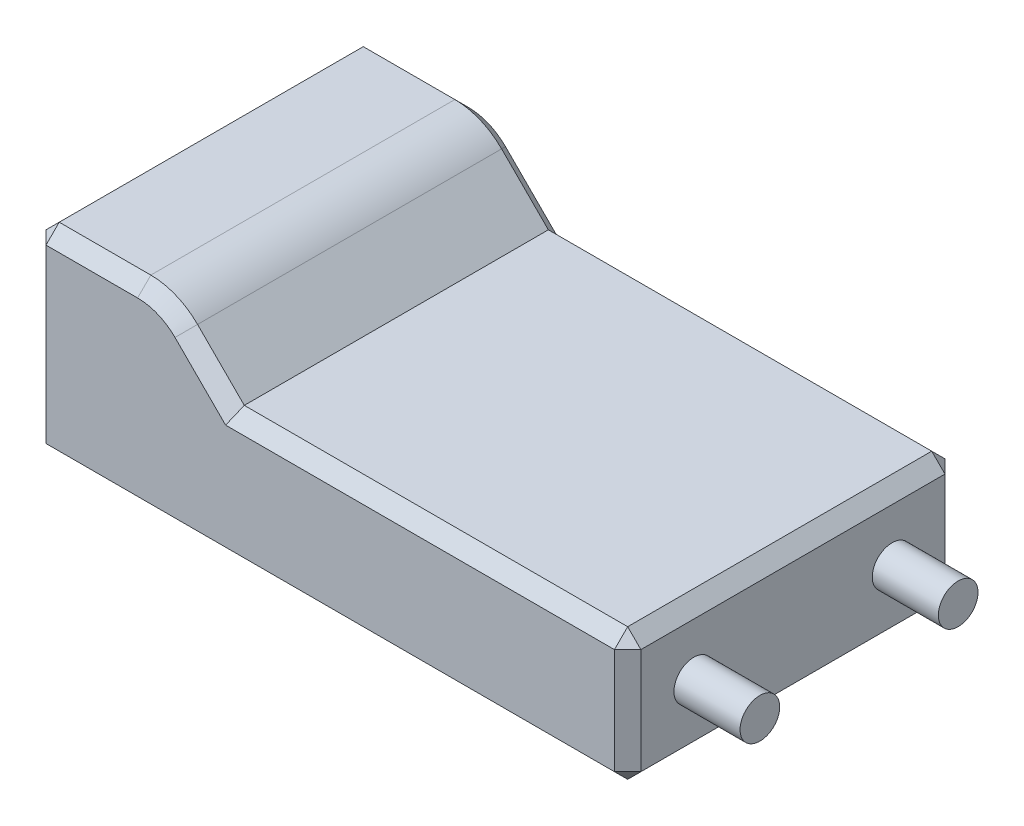
SolidWorks part; units mm, degrees
note: The reader was unsure of these and kept them because the rebuilt part matched: shared geometry of "草图1<4>".
ref_plane "前视基准面" through (0, 0, 0) normal (0, 0, 1) x (1, 0, 0)
ref_plane "上视基准面" through (0, 0, 0) normal (0, 1, 0) x (1, 0, 0)
ref_plane "右视基准面" through (0, 0, 0) normal (1, 0, 0) x (0, 0, -1)
sketch "草图1" plane through (0, 0, 0) normal (0, 1, 0) x (1, 0, 0)
  line L8 (-22.5, 12.5) -> (22.5, 12.5)
  line L9 (-22.5, 12.5) -> (-22.5, -12.5)
  line L10 (22.5, 12.5) -> (22.5, -12.5)
  line L11 (-22.5, -12.5) -> (22.5, -12.5)
  line L12 (-22.5, 12.5) -> (22.5, -12.5) construction
  line L13 (22.5, 12.5) -> (-22.5, -12.5) construction
  line L14 (-22.5, 12.5) -> (-12.5, 12.5)
  line L15 (-12.5, 12.5) -> (-12.5, -12.5)
  point P1 (0, 0)
  dimension "D1" = 45
  dimension "D2" = 25
  dimension "D3" = 10
extrude "凸台-拉伸1" add sketch "草图1" along normal blind 10 contours L8 L15 L11 L10
extrude "凸台-拉伸2" add sketch "草图1<4>" along normal blind 15 contours L15 L8 L9 L11
sketch "草图1<4>" plane through (0, 0, 0) normal (0, 1, 0) x (1, 0, 0) same geometry as "草图1"
sketch "草图2" plane through (-22.5, 0, 0) normal (-1, 0, 0) x (0, 0, 1)
  line L0 (0, 15) -> (0, 0)
  line L1 (-12.5, 15) -> (12.5, 15) construction
  line L2 (-10, 14) -> (10, 14)
  line L3 (-10, 14) -> (-10, 1)
  line L4 (10, 14) -> (10, 1)
  line L5 (-10, 1) -> (10, 1)
  line L6 (-10, 14) -> (10, 1) construction
  line L7 (10, 14) -> (-10, 1) construction
  point P6 (0, 7.5)
  dimension "D1" = 20
  dimension "D2" = 13
extrude "切除-拉伸1" cut sketch "草图2" against normal blind 7 contours L0 L5 L4 L2 | L3 L5 L0 L2
sketch "草图3" plane through (0, 0, 12.5) normal (0, 0, 1) x (1, 0, 0)
  line L0 (-12.5, 15) -> (-12.5, 10)
  line L1 (-12.5, 15) -> (-12.5, 10)
  line L2 (-12.5, 10) -> (-10, 10)
  line L3 (-12.5, 12.5) -> (-12.5, 10)
  line L4 (-12.5, 15) -> (-7.5, 10)
  dimension "D1" = 2.5
extrude "凸台-拉伸3" add sketch "草图3" against normal through all
fillet "圆角1" radius 5 1 edges at (-12.5, 15, 0)
chamfer "倒角1" distance 1 angle 45 18 edges at (-9.2678, 11.7678, -12.5) (-12.6577, 14.6194, -12.5) (7.5, 10, 12.5) (22.5, 5, 12.5) (0, 0, 12.5) (-22.5, 7.5, 12.5) (-9.2678, 11.7678, 12.5) (-12.6577, 14.6194, 12.5) (-18.5355, 15, 12.5) (-22.5, 0, 0) (22.5, 0, 0) (22.5, 10, 0) (7.5, 10, -12.5) (22.5, 5, -12.5) (0, 0, -12.5) (-22.5, 7.5, -12.5) (-18.5355, 15, -12.5) (-22.5, 15, 0)
sketch "草图5" plane through (22.5, 0, 0) normal (1, 0, 0) x (0, 0, -1)
  line L0 (-11.5, 5) -> (-7.5, 5)
  line L1 (-11.5, 9) -> (-11.5, 1) construction
  line L2 (0, 0) -> (0, 9)
  line L3 (11.5, 9) -> (-11.5, 9) construction
  circle A0 centre (-7.5, 5) radius 1.5
  circle A1 centre (7.5, 5) radius 1.5
  dimension "D2" = 3
  dimension "D1" = 4
extrude "凸台-拉伸4" add sketch "草图5" along normal blind 5
